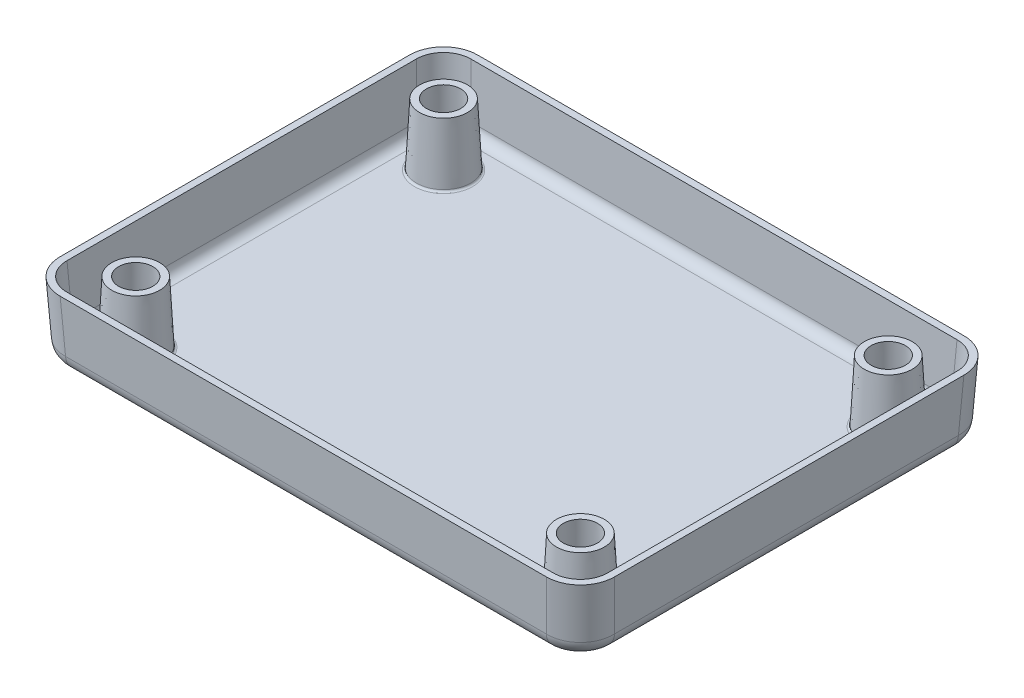
SolidWorks part; units mm, degrees
ref_plane "Front Plane" through (0, 0, 0) normal (0, 0, 1) x (1, 0, 0)
ref_plane "Top Plane" through (0, 0, 0) normal (0, 1, 0) x (1, 0, 0)
ref_plane "Right Plane" through (0, 0, 0) normal (1, 0, 0) x (0, 0, -1)
sketch "BOSS" plane through (0, 0, 0) normal (0, 1, 0) x (1, 0, 0)
  line L0 (82.55, 57.15) -> (101.6, 57.15) construction
  line L1 (0, 0) -> (101.6, 0)
  line L2 (0, 0) -> (0, 76.2)
  line L3 (0, 76.2) -> (101.6, 76.2)
  line L4 (101.6, 0) -> (101.6, 76.2)
  line L5 (82.55, 57.15) -> (82.55, 76.2) construction
  line L6 (0, 0) -> (0, -20.2965) construction
  line L7 (0, 0) -> (-16.6599, 0) construction
  circle A0 centre (82.55, 57.15) radius 6.35
  dimension "HOLE.SIZE" = 12.7
  dimension "EDGE.DISTANCE" = 19.05
  dimension "WIDTH" = 203.2
  dimension "HEIGHT" = 152.4
extrude "MAIN_BOSS" add sketch "BOSS" along normal blind 25.4
draft "Draft1" type of draft neutral plane draft angle 3 faces to draft 2 face at (50.8, 12.7, -76.2) face at (101.6, 12.7, -38.1) neutral plane through (0, 0, 0) neutral plane normal (0, -1, 0) parameters "D1"=3
draft "Draft2" type of draft neutral plane draft angle 3 faces to draft 1 face at (82.55, 25.4, -50.8) neutral plane through (0, 25.4, 0) neutral plane normal (0, 1, 0) reverse direction yes parameters "D1"=3
fillet "Fillet1" radius 12.7 1 edges at (102.2656, 12.7, -76.8656)
fillet "Fillet2" radius 6.35 3 edges at (44.4587, 0, -76.2) (97.8875, 0, -72.4875) (101.6, 0, -31.7587)
shell "Shell1" thickness 2.54 removed face at (59.7479, 25.4, -44.5079) removed face at (60.3242, 11.1105, 0) removed face at (0, 11.1105, -45.0842)
fillet "Fillet3" radius 0.762 1 edges at (82.55, 2.54, -67.2415)
fillet "Fillet4" radius 0.762 1 edges at (82.55, 0, -64.8312)
mirror "Mirror1" about plane through (0, 25.4, 0) normal (1, 0, 0) of bodies 101
mirror "Mirror2" about plane through (0, 25.4, 0) normal (0, 0, -1) of bodies 102
